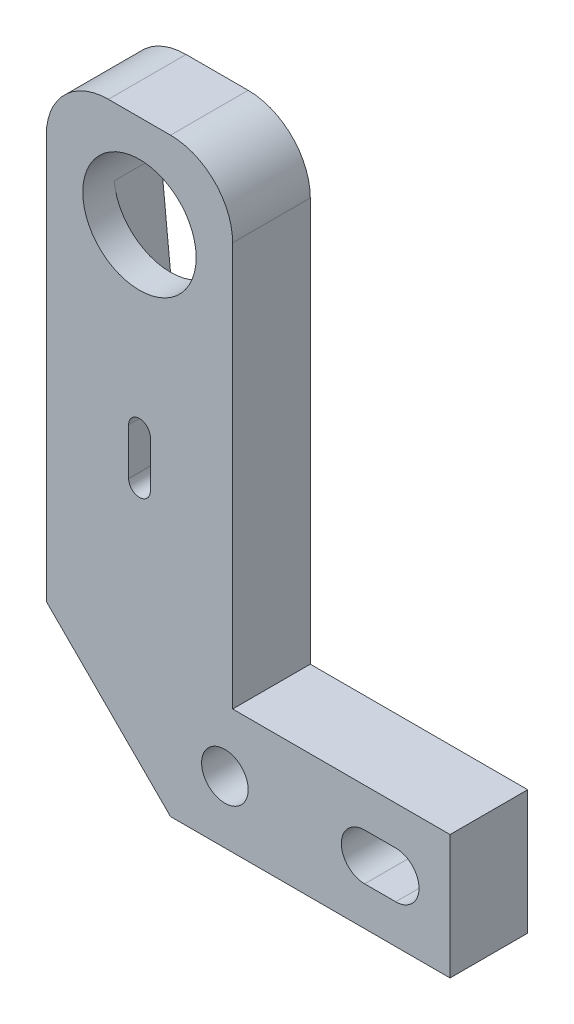
SolidWorks part; units mm, degrees
ref_plane "Plano frontal" through (0, 0, 0) normal (0, 0, 1) x (1, 0, 0)
ref_plane "Plano superior" through (0, 0, 0) normal (0, 1, 0) x (1, 0, 0)
ref_plane "Plano direito" through (0, 0, 0) normal (1, 0, 0) x (0, 0, -1)
sketch "Esboço1" plane through (0, 0, 0) normal (0, 0, 1) x (1, 0, 0)
  line L0 (0, 0) -> (0, -24) construction
  line L1 (-6, 2) -> (-6, -24)
  line L2 (6, 2) -> (6, -24)
  line L3 (20, -32) -> (20, -24)
  line L4 (-6, -24) -> (2, -32)
  line L5 (2, -32) -> (20, -32)
  line L6 (20, -24) -> (6, -24)
  line L7 (5.5, -28) -> (16.5, -28) construction
  line L8 (-2, 6) -> (2, 6)
  line L9 (2.2387, -14.225) -> (3.6317, -0.365)
  line L10 (-3.6317, -0.365) -> (-2.2387, -14.225)
  line L11 (0, -14.5) -> (0, -11.5) construction
  line L12 (-0.7, -14.5) -> (-0.7, -11.5)
  line L13 (0.7, -14.5) -> (0.7, -11.5)
  line L14 (16.5, -26.5) -> (14.5, -26.5)
  line L15 (6, 0) -> (6, -24) construction
  line L16 (14.5, -29.5) -> (16.5, -29.5)
  line L17 (-6, 0) -> (-6, -24) construction
  circle A0 centre (5.5, -28) radius 1.5
  arc A1 (16.5, -29.5) -> (16.5, -26.5) centre (16.5, -28) ccw
  circle A2 centre (0, 0) radius 3.65
  arc A3 (-2.2387, -14.225) -> (2.2387, -14.225) centre (0, -14) ccw
  arc A4 (-0.7, -14.5) -> (0.7, -14.5) centre (0, -14.5) ccw
  arc A5 (0.7, -11.5) -> (-0.7, -11.5) centre (0, -11.5) ccw
  arc A6 (14.5, -26.5) -> (14.5, -29.5) centre (14.5, -28) ccw
  arc A7 (6, 2) -> (2, 6) centre (2, 2) ccw
  arc A8 (-6, 2) -> (-2, 6) centre (-2, 2) cw
  point P15 (-2, -28)
  point P25 (0, -13)
  point P36 (11, -28)
  point P37 (11, -32)
  point P45 (-6, 6)
  dimension "D3" = 3
  dimension "D8" = 7.3
  dimension "D11" = 4.5
  dimension "D12" = 0.7
  dimension "D16" = 4
  dimension "D4" = 8
  dimension "D6" = 18
  dimension "D7" = 30
  dimension "D9" = 6
  dimension "D10" = 14
  dimension "D13" = 3
  dimension "D14" = 0.5
  dimension "D15" = 2
  dimension "D5" = 8
  dimension "D17" = 8
  dimension "D1" = 6
  dimension "D2" = 6
extrude "Ressalto-extrusão1" add sketch "Esboço1" along normal blind 5 contours L8 L1 L4 L5 L2 A2 L9 A3 L10 A1 A0 | L0 A2 L10 A3 | A2 L0 A3 L9 region at (3.3272, -17.5644, 0) region at (0, -8.5081, 0)
extrude "Corte-extrusão1" cut sketch "Esboço1<3>" along normal blind 3 contours L10 A3 L9 A2 A5 L13 A4 L12 region at (0, -8.5081, 0)
sketch "Esboço1<3>" plane through (0, 0, 0) normal (0, 0, 1) x (1, 0, 0) same geometry as "Esboço1"
equation "\"D2@Esboço1\"=\"D1@Esboço1\""
